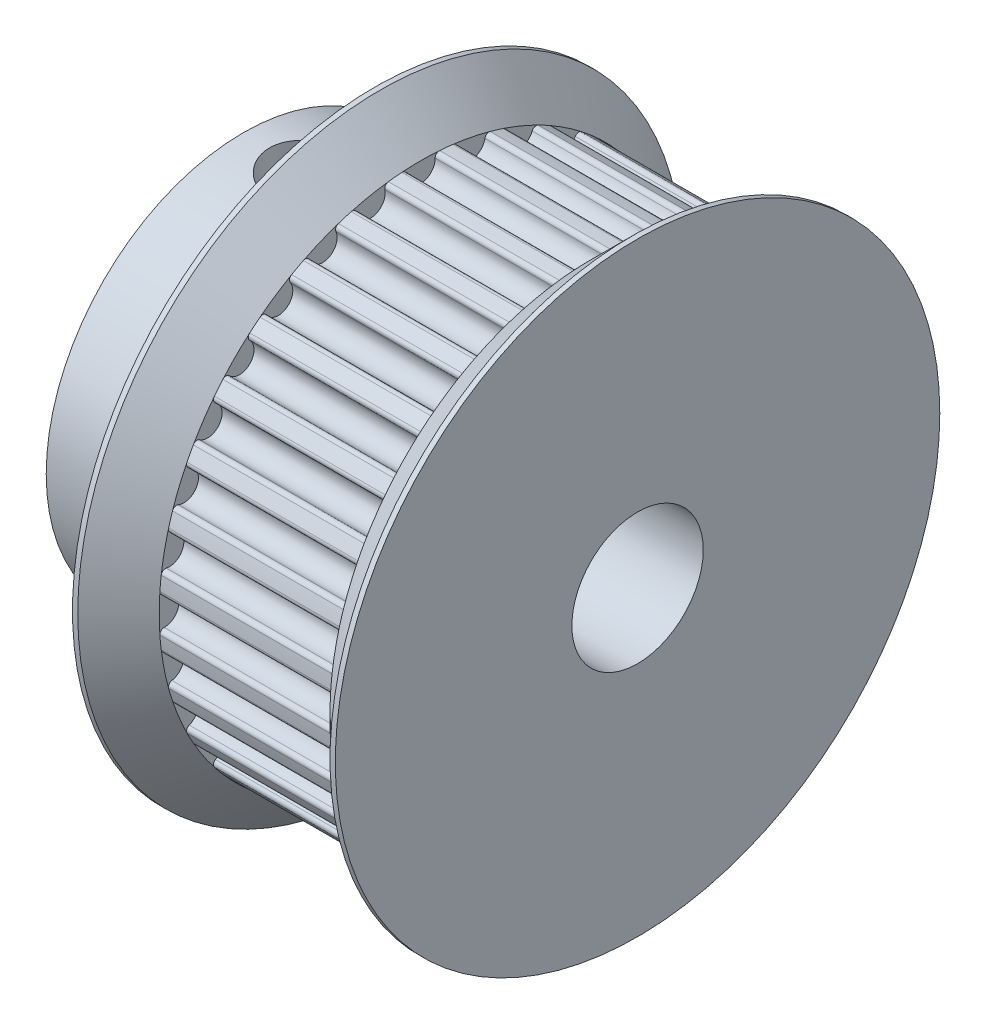
SolidWorks part; units mm, degrees
ref_plane "Front Plane" through (0, 0, 0) normal (0, 0, 1) x (1, 0, 0)
ref_plane "Top Plane" through (0, 0, 0) normal (0, 1, 0) x (1, 0, 0)
ref_plane "Right Plane" through (0, 0, 0) normal (1, 0, 0) x (0, 0, -1)
sketch "Sketch1" plane through (0, 0, 0) normal (0, 1, 0) x (1, 0, 0)
  line L0 (0, 0) -> (-15.0604, 0) construction
  line L1 (-1.75, 9.95) -> (-8.25, 9.95)
  line L2 (-10, 11.5) -> (-10, 2.5)
  line L3 (-10, 2.5) -> (0, 2.5)
  line L4 (0, 2.5) -> (0, 11.5)
  line L5 (-0.2, 11.5) -> (-1.75, 9.95)
  line L6 (-5, 9.95) -> (-5, 11.9782) construction
  line L7 (-9.8, 11.5) -> (-8.25, 9.95)
  line L8 (-10, 11.5) -> (-9.8, 11.5)
  line L9 (-0.2, 11.5) -> (0, 11.5)
  dimension "D1" = 6.5
  dimension "D2" = 19.9
  dimension "D3" = 23
  dimension "D4" = 5
  dimension "D5" = 135
  dimension "D6" = 10
revolve "Revolve1" add sketch "Sketch1" angle 360 about L0
ref_plane "Plane1" through (-1.75, 0, 0) normal (1, 0, 0) x (0, 0, -1)
ref_plane "Plane2" through (-8.25, 0, 0) normal (1, 0, 0) x (0, 0, -1)
sketch "Sketch2" plane through (-1.75, 0, 0) normal (1, 0, 0) x (0, 0, -1)
  circle A0 centre (0, 9.75) radius 0.55
  circle A1 centre (1.9021, 9.5627) radius 0.55
  circle A2 centre (3.7312, 9.0078) radius 0.55
  circle A3 centre (5.4168, 8.1068) radius 0.55
  circle A4 centre (6.8943, 6.8943) radius 0.55
  circle A5 centre (8.1068, 5.4168) radius 0.55
  circle A6 centre (9.0078, 3.7312) radius 0.55
  circle A7 centre (9.5627, 1.9021) radius 0.55
  circle A8 centre (9.75, 0) radius 0.55
  circle A9 centre (9.5627, -1.9021) radius 0.55
  circle A10 centre (9.0078, -3.7312) radius 0.55
  circle A11 centre (8.1068, -5.4168) radius 0.55
  circle A12 centre (6.8943, -6.8943) radius 0.55
  circle A13 centre (5.4168, -8.1068) radius 0.55
  circle A14 centre (3.7312, -9.0078) radius 0.55
  circle A15 centre (1.9021, -9.5627) radius 0.55
  circle A16 centre (0, -9.75) radius 0.55
  circle A17 centre (-1.9021, -9.5627) radius 0.55
  circle A18 centre (-3.7312, -9.0078) radius 0.55
  circle A19 centre (-5.4168, -8.1068) radius 0.55
  circle A20 centre (-6.8943, -6.8943) radius 0.55
  circle A21 centre (-8.1068, -5.4168) radius 0.55
  circle A22 centre (-9.0078, -3.7312) radius 0.55
  circle A23 centre (-9.5627, -1.9021) radius 0.55
  circle A24 centre (-9.75, 0) radius 0.55
  circle A25 centre (-9.5627, 1.9021) radius 0.55
  circle A26 centre (-9.0078, 3.7312) radius 0.55
  circle A27 centre (-8.1068, 5.4168) radius 0.55
  circle A28 centre (-6.8943, 6.8943) radius 0.55
  circle A29 centre (-5.4168, 8.1068) radius 0.55
  circle A30 centre (-3.7312, 9.0078) radius 0.55
  circle A31 centre (-1.9021, 9.5627) radius 0.55
  point P68 (0, 0)
  dimension "D1" = 9.75
  dimension "D2" = 1.1
  dimension "D3" = 32
extrude "Cut-Extrude1" cut sketch "Sketch2" against normal up to surface (6.5 mm away) up to plane "Plane2"
fillet "Fillet1" radius 0.16 64 edges at (-5, -0.5174, 9.9365) (-5, 0.5174, 9.9365) (-5, 1.4311, 9.8466) (-5, 2.446, 9.6447) (-5, 3.3245, 9.3782) (-5, 4.2806, 8.9822) (-5, 5.0902, 8.5494) (-5, 5.9506, 7.9745) (-5, 6.6603, 7.3921) (-5, 7.3921, 6.6603) (-5, 7.9745, 5.9506) (-5, 8.5494, 5.0902) (-5, 8.9822, 4.2806) (-5, 9.3782, 3.3245) (-5, 9.6447, 2.446) (-5, 9.8466, 1.4311) (-5, 9.9365, 0.5174) (-5, 9.9365, -0.5174) (-5, 9.8466, -1.4311) (-5, 9.6447, -2.446) (-5, 9.3782, -3.3245) (-5, 8.9822, -4.2806) (-5, 8.5494, -5.0902) (-5, 7.9745, -5.9506) (-5, 6.6603, -7.3921) (-5, 7.3921, -6.6603) (-5, 5.9506, -7.9745) (-5, 5.0902, -8.5494) (-5, 4.2806, -8.9822) (-5, 3.3245, -9.3782) (-5, 2.446, -9.6447) (-5, 1.4311, -9.8466) (-5, 0.5174, -9.9365) (-5, -0.5174, -9.9365) (-5, -1.4311, -9.8466) (-5, -2.446, -9.6447) (-5, -3.3245, -9.3782) (-5, -4.2806, -8.9822) (-5, -5.0902, -8.5494) (-5, -5.9506, -7.9745) (-5, -6.6603, -7.3921) (-5, -7.3921, -6.6603) (-5, -7.9745, -5.9506) (-5, -8.5494, -5.0902) (-5, -8.9822, -4.2806) (-5, -9.3782, -3.3245) (-5, -9.6447, -2.446) (-5, -9.8466, -1.4311) (-5, -9.9365, -0.5174) (-5, -9.9365, 0.5174) (-5, -9.8466, 1.4311) (-5, -9.6447, 2.446) (-5, -9.3782, 3.3245) (-5, -8.9822, 4.2806) (-5, -8.5494, 5.0902) (-5, -7.9745, 5.9506) (-5, -1.4311, 9.8466) (-5, -2.446, 9.6447) (-5, -3.3245, 9.3782) (-5, -4.2806, 8.9822) (-5, -5.0902, 8.5494) (-5, -5.9506, 7.9745) (-5, -6.6603, 7.3921) (-5, -7.3921, 6.6603)
sketch "Sketch3" plane through (-10, 0, 0) normal (-1, 0, 0) x (0, 0, 1)
  circle A0 centre (0, 0) radius 7.5
  circle A1 centre (0, 0) radius 2.5
  dimension "D1" = 15
  dimension "D2" = 5
extrude "Boss-Extrude1" add sketch "Sketch3" along normal blind 5
sketch "Sketch4" plane through (0, 0, 0) normal (0, 1, 0) x (1, 0, 0)
  line L0 (-15, 7.5) -> (-15, -7.5) construction
  circle A0 centre (-12.5, 0) radius 1.5
  dimension "D1" = 2.5
  dimension "D2" = 3
extrude "Cut-Extrude2" cut sketch "Sketch4" against normal through all and the other way through all
